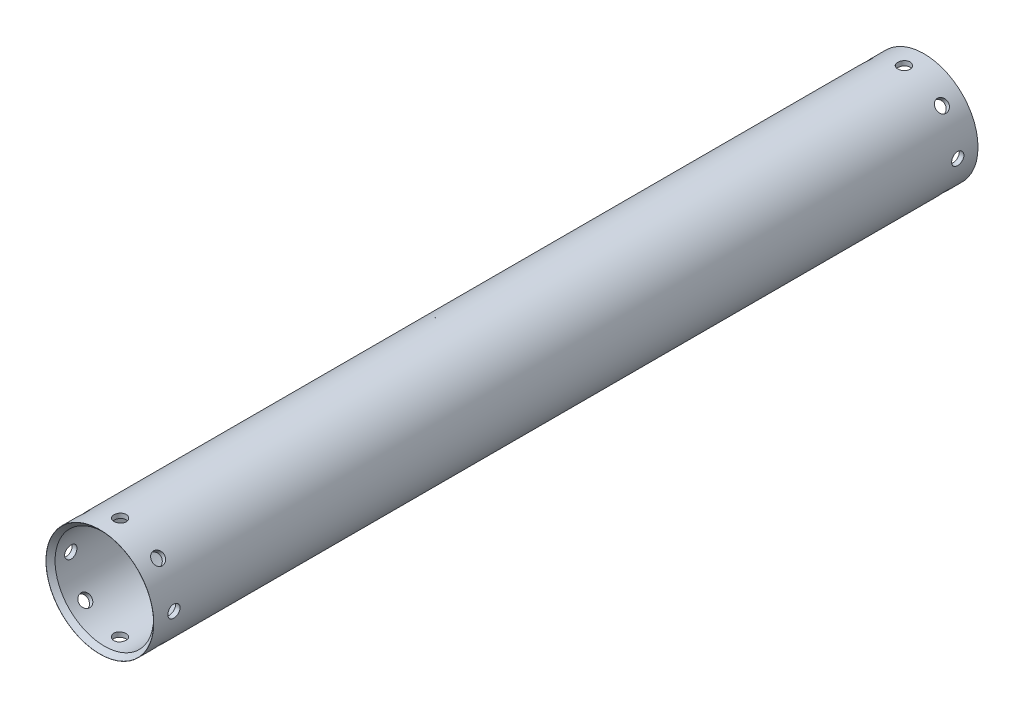
SolidWorks part; units mm, degrees
material "Acrílico (Impacto medio-alto)"
ref_plane "Front Plane" through (0, 0, 0) normal (0, 0, 1) x (1, 0, 0)
ref_plane "Top Plane" through (0, 0, 0) normal (0, 1, 0) x (1, 0, 0)
ref_plane "Right Plane" through (0, 0, 0) normal (1, 0, 0) x (0, 0, -1)
sketch "Sketch1" plane through (0, 0, 0) normal (0, 0, 1) x (1, 0, 0)
  circle A0 centre (0, 0) radius 34.675
  circle A1 centre (0, 0) radius 38.275
extrude "Boss-Extrude1" add sketch "Sketch1" along normal blind 585 contours A1
sketch "Sketch2" plane through (0, 0, 585) normal (0, 0, 1) x (1, 0, 0)
  circle A0 centre (0, 0) radius 34.975
extrude "Cut-Extrude1" cut sketch "Sketch2" against normal blind 585 contours A0
sketch "Sketch6" plane through (0, 0, 0) normal (0, 1, 0) x (1, 0, 0)
  line L0 (-38.275, -585) -> (38.275, -585) construction
  line L1 (38.275, -585) -> (38.275, 0) construction
  circle A0 centre (0, -570.65) radius 4.35
  dimension "D2" = 8.7
  dimension "D1" = 14.35
  dimension "D3" = 38.275
extrude "Cut-Extrude2" cut sketch "Sketch6" against normal through all and the other way through all
sketch "Sketch7" plane through (0, 0, 0) normal (1, 0, 0) x (0, 0, -1)
  line L0 (-585, 38.275) -> (-585, -38.275) construction
  line L1 (-566.3, -38.275) -> (0, -38.275) construction
  circle A0 centre (-570.65, 0) radius 4.35
  dimension "D2" = 8.7
  dimension "D1" = 14.35
  dimension "D3" = 38.275
extrude "Cut-Extrude3" cut sketch "Sketch7" against normal through all and the other way through all contours A0
sketch "Sketch8" plane through (0, 0, 0) normal (1, 0, 0) x (0, 0, -1)
  line L0 (0, 42.1025) -> (0, -42.1025) construction
  line L1 (-566.3, -38.275) -> (0, -38.275) construction
  circle A0 centre (-14.35, 0) radius 4.35
  dimension "D1" = 8.7
  dimension "D2" = 14.35
  dimension "D3" = 38.275
extrude "Cut-Extrude4" cut sketch "Sketch8" against normal through all and the other way through all
sketch "Sketch9" plane through (0, 0, 0) normal (0, 1, 0) x (1, 0, 0)
  line L0 (-42.1025, 0) -> (42.1025, 0) construction
  line L1 (38.275, -566.3) -> (38.275, -18.7) construction
  circle A0 centre (0, -14.35) radius 4.35
  dimension "D1" = 8.7
  dimension "D2" = 14.35
  dimension "D3" = 38.275
extrude "Cut-Extrude5" cut sketch "Sketch9" against normal through all and the other way through all
ref_plane "Plane1" through (27.0645, -27.0645, 0) normal (0.7071, -0.7071, 0) x (0, 0, -1)
sketch "Sketch10" plane through (27.0645, -27.0645, 0) normal (0.7071, -0.7071, 0) x (0, 0, -1)
  line L0 (-585, 38.275) -> (-585, -38.275) construction
  line L3 (-585, -38.275) -> (0, -38.275) construction
  circle A0 centre (-570.65, 0) radius 4.35
  dimension "D1" = 8.7
  dimension "D3" = 38.275
  dimension "D2" = 14.35
extrude "Cut-Extrude6" cut sketch "Sketch10" along normal through all and the other way through all
sketch "Sketch11" plane through (27.0645, -27.0645, 0) normal (0.7071, -0.7071, 0) x (0, 0, -1)
  line L0 (0, 42.1025) -> (0, -42.1025) construction
  line L1 (-585, -38.275) -> (0, -38.275) construction
  circle A0 centre (-14.35, 0) radius 4.35
  dimension "D1" = 8.7
  dimension "D2" = 14.35
  dimension "D3" = 38.275
extrude "Cut-Extrude7" cut sketch "Sketch11" against normal through all and the other way through all contours A0
ref_plane "Plane2" through (-27.0645, -27.0645, 0) normal (-0.7071, -0.7071, 0) x (0, 0, 1)
sketch "Sketch12" plane through (-27.0645, -27.0645, 0) normal (-0.7071, -0.7071, 0) x (0, 0, 1)
  line L0 (18.7, -38.275) -> (566.3, -38.275) construction
  line L1 (585, -38.275) -> (585, 38.275) construction
  circle A0 centre (570.65, 0) radius 4.35
  dimension "D1" = 8.7
  dimension "D2" = 38.275
  dimension "D3" = 14.35
extrude "Cut-Extrude8" cut sketch "Sketch12" against normal blind 585 and the other way blind 585 contours A0
sketch "Sketch13" plane through (-27.0645, -27.0645, 0) normal (-0.7071, -0.7071, 0) x (0, 0, 1)
  line L0 (0, 38.275) -> (0, -38.275) construction
  line L1 (18.7, -38.275) -> (566.3, -38.275) construction
  circle A0 centre (14.35, 0) radius 4.35
  dimension "D1" = 8.7
  dimension "D2" = 14.35
  dimension "D3" = 38.275
extrude "Cut-Extrude9" cut sketch "Sketch13" along normal blind 585 and the other way blind 585 contours A0
chamfer "Chamfer1" distance 3.2 angle 45 1 edges at (34.975, 0, 585)
chamfer "Chamfer2" distance 3.2 angle 45 1 edges at (34.975, 0, 0)
